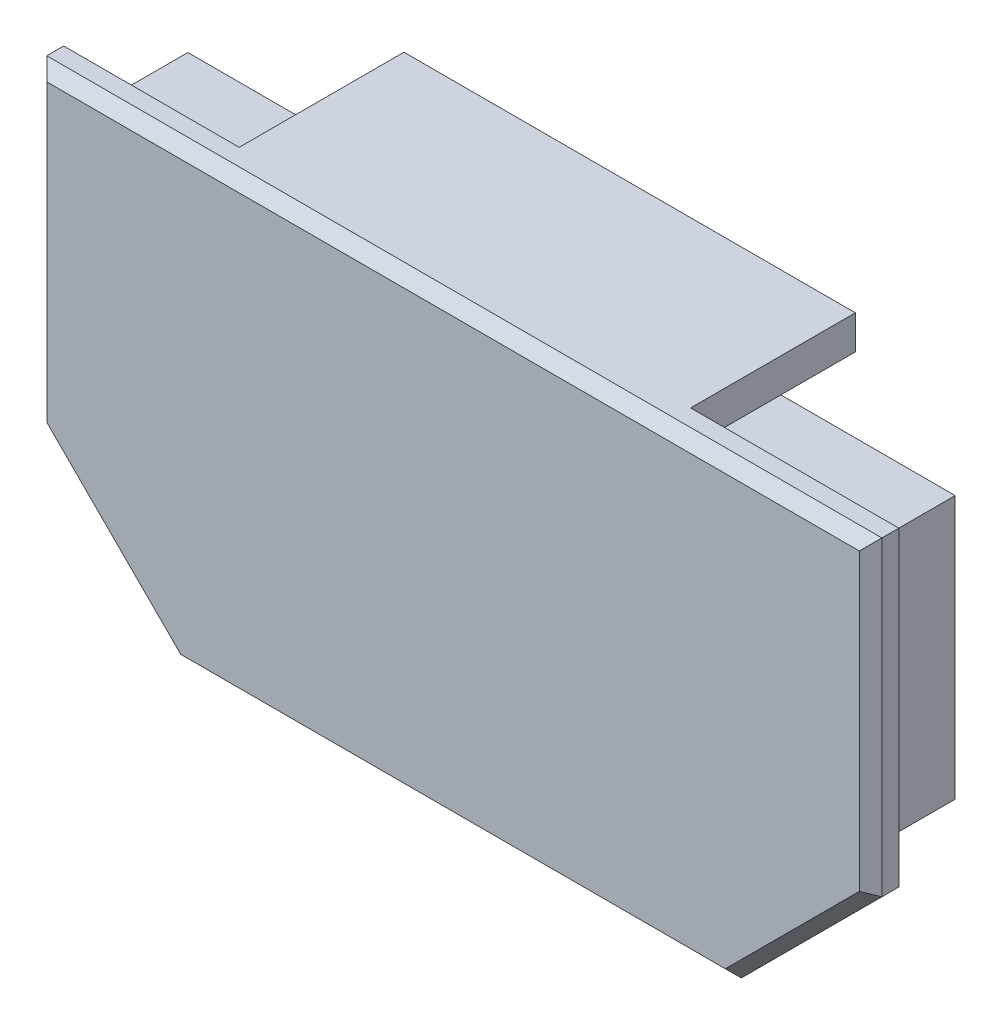
SolidWorks part; units mm, degrees
material "ABS"
ref_plane "Front Plane" through (0, 0, 0) normal (0, 0, 1) x (1, 0, 0)
ref_plane "Top Plane" through (0, 0, 0) normal (0, 1, 0) x (1, 0, 0)
ref_plane "Right Plane" through (0, 0, 0) normal (1, 0, 0) x (0, 0, -1)
sketch "Servo Bracket Reference" plane through (0, 0, 0) normal (0, 0, 1) x (1, 0, 0)
  line L0 (-37, 20) -> (37, 20) construction
  line L1 (-37, -3.3) -> (-20.3, -20) construction
  line L34 (-37, 20) -> (-37, -7.5426) construction
  line L35 (-37, -7.5426) -> (-24.5426, -20) construction
  line L36 (-24.5426, -20) -> (24.5426, -20) construction
  line L37 (24.5426, -20) -> (37, -7.5426) construction
  line L38 (37, -7.5426) -> (37, 20) construction
  point P0 (0, 20)
  dimension "D3" = 74
  dimension "D1" = 40
  dimension "D5" = 20
  dimension "D2" = 3
  dimension "D4" = 16.7
sketch "Sketch2" plane through (0, 0, 0) normal (0, 0, 1) x (1, 0, 0)
  line L18 (37, -7.5426) -> (37, 20) construction
  line L19 (24.5426, -20) -> (37, -7.5426) construction
  line L20 (-24.5426, -20) -> (24.5426, -20) construction
  line L21 (-37, 20) -> (-37, -7.5426) construction
  line L22 (-37, -7.5426) -> (-24.5426, -20) construction
  line L23 (-37, 20) -> (37, 20) construction
  line L24 (37, -7.5426) -> (37, 20) construction
  line L25 (24.5426, -20) -> (37, -7.5426) construction
  line L26 (-24.5426, -20) -> (24.5426, -20) construction
  line L27 (-37, 20) -> (-37, -7.5426) construction
  line L28 (-37, -7.5426) -> (-24.5426, -20) construction
  line L29 (-37, 20) -> (37, 20) construction
  line L36 (34, -6.3) -> (34, 17)
  line L37 (-34, 17) -> (34, 17)
  line L38 (-34, 17) -> (-34, -6.3)
  line L39 (-34, -6.3) -> (-23.3, -17)
  line L40 (-23.3, -17) -> (23.3, -17)
  line L41 (23.3, -17) -> (34, -6.3)
  line L42 (32, -5.4716) -> (32, 15)
  line L43 (-32, 15) -> (32, 15)
  line L44 (-32, 15) -> (-32, -5.4716)
  line L45 (-32, -5.4716) -> (-22.4716, -15)
  line L46 (-22.4716, -15) -> (22.4716, -15)
  line L47 (22.4716, -15) -> (32, -5.4716)
  dimension "D1" = 3
  dimension "D2" = 2
extrude "Press Fit Wall Extrude" add sketch "Sketch2" against normal blind 8
sketch "Sketch3" plane through (0, 0, 0) normal (0, 0, 1) x (1, 0, 0)
  line L6 (24.5426, -20) -> (37, -7.5426) construction
  line L7 (37, -7.5426) -> (37, 20) construction
  line L8 (-37, 20) -> (37, 20) construction
  line L9 (-37, 20) -> (-37, -7.5426) construction
  line L10 (-37, -7.5426) -> (-24.5426, -20) construction
  line L11 (-24.5426, -20) -> (24.5426, -20) construction
  line L24 (24.5426, -20) -> (37, -7.5426)
  line L25 (37, -7.5426) -> (37, 20)
  line L26 (-37, 20) -> (37, 20)
  line L27 (-37, 20) -> (-37, -7.5426)
  line L28 (-37, -7.5426) -> (-24.5426, -20)
  line L29 (-24.5426, -20) -> (24.5426, -20)
extrude "Main Lid Extrude" add sketch "Sketch3" along normal blind 2.5
chamfer "Main Lid Chamfer" distance 1 angle 45 6 edges at (37, 6.2287, 2.5) (30.7713, -13.7713, 2.5) (-30.7713, -13.7713, 2.5) (-37, 6.2287, 2.5) (0, 20, 2.5) (0, -20, 2.5)
sketch "Sketch4" plane through (0, -20, 0) normal (0, -1, 0) x (1, 0, 0)
  line L0 (-4, 0) -> (4, 0)
  line L5 (-37, 0) -> (37, 0) construction
  line L6 (4, 0) -> (2.2679, 1)
  line L7 (2.2679, 1) -> (-2.2679, 1)
  line L8 (-2.2679, 1) -> (-4, 0)
  point P4 (0, 0)
  dimension "D1" = 8
  dimension "D2" = 30
  dimension "D3" = 1
extrude "Main Lid Tab Cut" cut sketch "Sketch4" against normal up to surface (3 mm away) up to face at (0, -17, -4)
sketch "Sketch5" plane through (0, 0, 0) normal (0, 0, -1) x (-1, 0, 0)
  line L0 (-37, 20) -> (37, 20) construction
  line L1 (-18.55, 20) -> (21.45, 20)
  line L2 (-18.55, 20) -> (-18.55, 17)
  line L3 (-18.55, 17) -> (21.45, 17)
  line L4 (21.45, 20) -> (21.45, 17)
  line L5 (-34, 17) -> (34, 17) construction
  line L7 (-37, -7.5426) -> (-37, 20) construction
  dimension "D1" = 40
  dimension "D2" = 18.45
extrude "Servo Wall Extrude" add sketch "Sketch5" along normal blind 14.6
equation "\"D5@Servo Bracket Reference\"=\"D1@Servo Bracket Reference\"/2"
